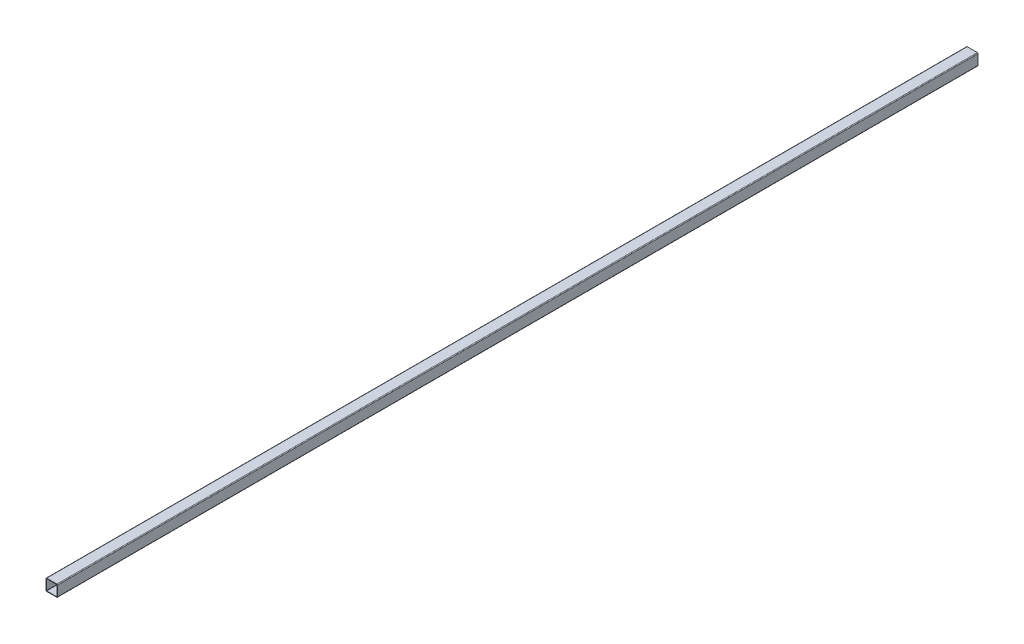
SolidWorks part; units mm, degrees
ref_plane "Front" through (0, 0, 0) normal (0, 0, 1) x (1, 0, 0)
ref_plane "Top" through (0, 0, 0) normal (0, 1, 0) x (1, 0, 0)
ref_plane "Right" through (0, 0, 0) normal (1, 0, 0) x (0, 0, -1)
sketch "inch square tube" plane through (0, 0, 0) normal (0, 0, 1) x (1, 0, 0)
  line L0 (0, 0) -> (-19.05, 0) construction
  line L1 (16.65, -19.05) -> (-16.65, -19.05)
  line L2 (19.05, -16.65) -> (19.05, 16.65)
  line L3 (16.65, 19.05) -> (-16.65, 19.05)
  line L4 (-19.05, -16.65) -> (-19.05, 16.65)
  line L5 (0, 0) -> (0, -19.05) construction
  line L7 (-16.65, 17.45) -> (16.65, 17.45)
  line L8 (-17.45, 16.65) -> (-17.45, -16.65)
  line L9 (-16.65, -17.45) -> (16.65, -17.45)
  line L10 (17.45, 16.65) -> (17.45, -16.65)
  circle A0 centre (0, 0) radius 14.1224 construction
  arc A1 (-16.65, -19.05) -> (-19.05, -16.65) centre (-16.65, -16.65) cw
  arc A2 (16.65, -19.05) -> (19.05, -16.65) centre (16.65, -16.65) ccw
  arc A3 (19.05, 16.65) -> (16.65, 19.05) centre (16.65, 16.65) ccw
  arc A4 (-16.65, 19.05) -> (-19.05, 16.65) centre (-16.65, 16.65) ccw
  arc A5 (16.65, 17.45) -> (17.45, 16.65) centre (16.65, 16.65) cw
  arc A6 (16.65, -17.45) -> (17.45, -16.65) centre (16.65, -16.65) ccw
  arc A7 (-17.45, -16.65) -> (-16.65, -17.45) centre (-16.65, -16.65) ccw
  arc A8 (-16.65, 17.45) -> (-17.45, 16.65) centre (-16.65, 16.65) ccw
  point P0 (0, 0)
  point P1 (-17.45, 0)
  point P4 (0, -17.45)
  point P12 (19.05, 0)
  point P13 (-19.05, 0)
  point P14 (0, 19.05)
  point P35 (-19.05, -19.05)
  point P36 (0, -19.05)
  point P37 (-19.05, 19.05)
  point P38 (19.05, 19.05)
  point P39 (19.05, -19.05)
  dimension "D2" = 14.1224
  dimension "D4" = 2.4
  dimension "D5" = 0.8
  dimension "D3" = 1.6
  dimension "D1" = 38.1
extrude "Boss-Extrude1" add sketch "inch square tube" along normal blind 3048
equation "\"D4@inch square tube\" = \"D3@inch square tube\" * 1.5"
equation "\"D5@inch square tube\" = \"D4@inch square tube\" - \"D3@inch square tube\""
equation "\"10feet\"=0.6"
